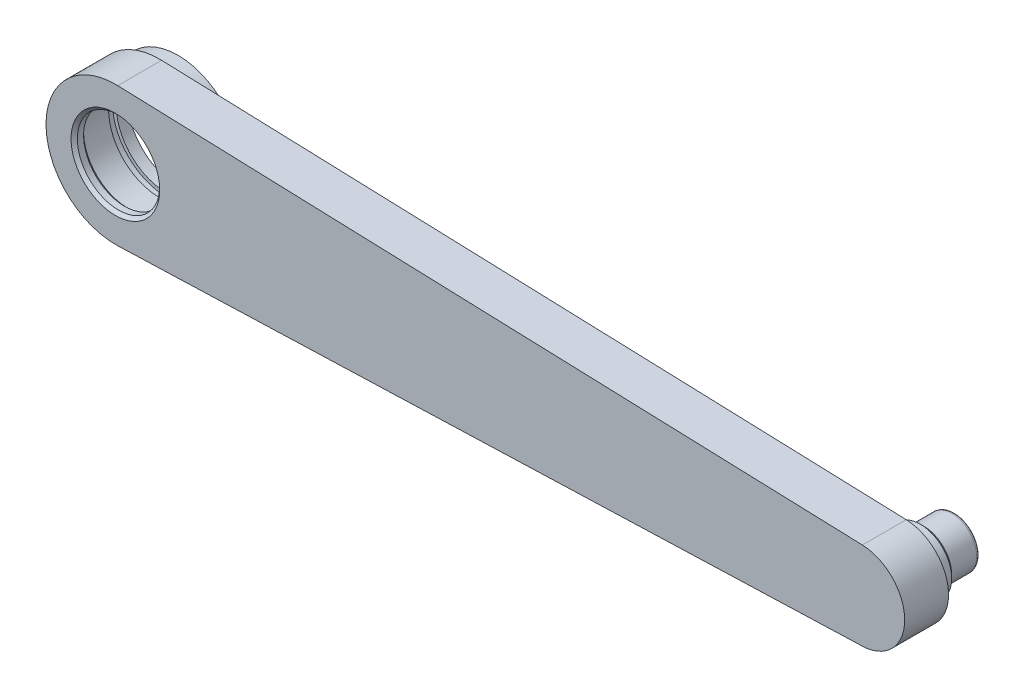
SolidWorks part; units mm, degrees
material "PEI"
ref_plane "前视基准面" through (0, 0, 0) normal (0, 0, 1) x (1, 0, 0)
ref_plane "上视基准面" through (0, 0, 0) normal (0, 1, 0) x (1, 0, 0)
ref_plane "右视基准面" through (0, 0, 0) normal (1, 0, 0) x (0, 0, -1)
other "Configuration Table"
sketch "草图1" plane through (0, 0, 0) normal (0, 0, 1) x (1, 0, 0)
  line L0 (0, 0) -> (119, 0) construction
  line L1 (0.3792, 11.0685) -> (119.2397, 6.9959)
  line L2 (0.3796, -11.0685) -> (119, -7)
  circle A0 centre (119, 0) radius 7
  circle A1 centre (0, 0) radius 8.075
  circle A2 centre (0, 0) radius 11.075
  dimension "D1" = 16.15
  dimension "D3" = 14
  dimension "D2" = 3
  dimension "D4" = 119
extrude "凸台-拉伸1" add sketch "草图1" along normal blind 7 contours A1 A2 | A2 L0 A0 L1 | L0 A2 L2 A0 | A0 region at (7.739, -7.4781, 0) region at (57.6854, 4.654, 0) region at (57.6797, -4.6531, 0) region at (114.2733, 4.8914, 0)
sketch "草图2" plane through (0, 0, 7) normal (0, 0, 1) x (1, 0, 0)
  circle A0 centre (0, 0) radius 8.075 construction
  circle A1 centre (0, 0) radius 8.075
  circle A2 centre (0, 0) radius 6.575
  dimension "D1" = 1.5
extrude "凸台-拉伸2" add sketch "草图2" against normal blind 2
sketch "草图3" plane through (0, 0, 0) normal (0, 0, -1) x (-1, 0, 0)
  arc A0 (-119.2397, 6.9959) -> (-119, -7) centre (-119, 0) ccw construction
  arc A1 (-119.2397, 6.9959) -> (-119, -7) centre (-119, 0) ccw
  circle A2 centre (-119, 0) radius 4
  dimension "D1" = 8
extrude "凸台-拉伸3" add sketch "草图3" along normal blind 10 contours A2 region at (119, 0, 0)
sketch "草图4" plane through (0, 0, 0) normal (0, 0, -1) x (-1, 0, 0)
  circle A0 centre (-119, 0) radius 4 construction
  circle A1 centre (-119, 0) radius 4
  circle A2 centre (-119, 0) radius 5
  dimension "D1" = 1
extrude "凸台-拉伸4" add sketch "草图4" along normal blind 3
chamfer "倒角1" distance 0.5 angle 45 4 edges at (6.575, 0, 7) (6.575, 0, 5) (114, 0, -3) (115, 0, -10)
chamfer "倒角2" [suppressed] distance 1 angle 45
sketch "草图5" plane through (0, 0, 0) normal (0, 0, -1) x (-1, 0, 0)
  line L0 (-0.1738, 5.072) -> (-119.0901, 0.9975)
  line L1 (-118.9996, -0.9965) -> (-0.174, -5.072)
  line L2 (-119, -7) -> (-0.3796, -11.0685)
  line L3 (-119, -7) -> (-0.3796, -11.0685)
  line L8 (-0.3792, 11.0685) -> (-119.2397, 6.9959)
  line L9 (-0.3792, 11.0685) -> (-119.2397, 6.9959)
  arc A0 (-119.0901, 0.9975) -> (-118.9996, -0.9965) centre (-119.0945, -0.0017) ccw
  arc A1 (-0.174, -5.072) -> (-0.1738, 5.072) centre (0, 0) ccw
  arc A2 (-0.3796, -11.0685) -> (-0.3792, 11.0685) centre (0, 0) ccw
  arc A3 (-0.3796, -11.0685) -> (-0.3792, 11.0685) centre (0, 0) ccw
  circle A6 centre (-119, 0) radius 5 construction
  arc A12 (-119.2397, 6.9959) -> (-119, -7) centre (-119, 0) ccw
  arc A13 (-119.2397, 6.9959) -> (-119, -7) centre (-119, 0) ccw
  circle A30 centre (0, 0) radius 8.575
  circle A31 centre (-119, 0) radius 5
  circle A32 centre (-119, 0) radius 10
  circle A33 centre (0, 0) radius 13.575
  dimension "D1" = 0
  dimension "D3" = 5
extrude "切除-拉伸1" cut sketch "草图5" against normal up to surface (7 mm away) contours A33 L0 A32 L1 region at (52.3871, 0.0009, 0) up to face at (7.075, 0, 7)
sketch "草图6" plane through (0, 0, 0) normal (0, 0, -1) x (-1, 0, 0)
  line L0 (-109.0897, -1.3364) -> (-12.7572, -4.6404) construction
  line L1 (-12.7571, 4.6409) -> (-109.0902, 1.3401) construction
  line L2 (-109.0897, -1.3364) -> (-12.7572, -4.6404)
  line L3 (-12.7571, 4.6409) -> (-109.0902, 1.3401)
  line L4 (-12.8598, 7.6391) -> (-109.1929, 4.3384)
  line L5 (-109.1925, -4.3346) -> (-12.8601, -7.6387)
  line L6 (-109.1929, 4.3384) -> (-109.0902, 1.3401)
  line L7 (-109.0897, -1.3364) -> (-109.1925, -4.3346)
  line L8 (-12.8598, 7.6391) -> (-12.7571, 4.6409)
  line L9 (-12.7572, -4.6404) -> (-12.8601, -7.6387)
  dimension "D1" = 3
extrude "切除-拉伸2" cut sketch "草图6" against normal blind 5
sketch "草图7" plane through (0, 0, 0) normal (0, 1, 0) x (1, 0, 0)
  line L0 (122.5, 10) -> (115.5, 10) construction
  line L1 (122.5, 10) -> (115.5, 10)
  line L2 (119, 10) -> (119, 0.7286) construction
  line L4 (115.3, 9) -> (115, 9)
  line L5 (115.3, 9) -> (115.3, 8)
  line L6 (115.3, 8) -> (115, 8)
  line L7 (115, 9) -> (115, 8)
  dimension "D1" = 1
  dimension "D2" = 4
  dimension "D3" = 3.7
  dimension "D4" = 2
revolve "切除-旋转1" [suppressed] cut sketch "草图7" angle 360 about L2
sketch "草图8" plane through (0, 0, -10) normal (0, 0, -1) x (-1, 0, 0)
  circle A0 centre (-119, 0) radius 4 construction
  circle A1 centre (-119, 0) radius 4
extrude "切除-拉伸3" cut sketch "草图8" against normal blind 2
fillet "圆角1" radius 0.5 1 edges at (115, 0, -8)
sketch "草图9" plane through (0, 0, -8) normal (0, 0, -1) x (-1, 0, 0)
  circle A0 centre (-119, 0) radius 2.2
  dimension "D1" = 4.4
extrude "切除-拉伸4" cut sketch "草图9" against normal blind 10
sketch "草图10" plane through (0, 0, 0) normal (0, 0, -1) x (-1, 0, 0)
  circle A0 centre (0, 0) radius 10.075
  circle A1 centre (0, 0) radius 8.075 construction
  circle A2 centre (0, 0) radius 8.075
  dimension "D1" = 2
extrude "凸台-拉伸5" add sketch "草图10" along normal blind 3
sketch "草图11" plane through (0, 0, 0) normal (0, 1, 0) x (1, 0, 0)
  line L0 (8.075, 3) -> (-8.075, 3) construction
  line L1 (5.1574, 1.2) -> (8.65, 1.2)
  line L2 (5.1574, 1.2) -> (5.1574, 0)
  line L3 (5.1574, 0) -> (8.65, 0)
  line L4 (8.65, 1.2) -> (8.65, 0)
  line L5 (0, 0) -> (0, 7.7818) construction
  dimension "D1" = 1.2
  dimension "D2" = 8.65
  dimension "D3" = 3
revolve "切除-旋转2" cut sketch "草图11" angle 360 about L5 region at (6.9037, 0, -0.6)
sketch "草图12" plane through (0, 0, 7) normal (0, 0, 1) x (1, 0, 0)
  line L0 (109.0897, -1.3364) -> (12.7572, -4.6404) construction
  line L1 (12.7571, 4.6409) -> (109.0902, 1.3401) construction
  line L2 (109.0897, -1.3364) -> (12.7572, -4.6404)
  line L3 (12.7571, 4.6409) -> (109.0902, 1.3401)
  arc A0 (109.0902, 1.3401) -> (109.0897, -1.3364) centre (119, 0) ccw construction
  arc A1 (12.7572, -4.6404) -> (12.7571, 4.6409) centre (0, 0) ccw construction
  arc A2 (109.0902, 1.3401) -> (109.0897, -1.3364) centre (119, 0) ccw
  arc A3 (12.7572, -4.6404) -> (12.7571, 4.6409) centre (0, 0) ccw
extrude "凸台-拉伸6" add sketch "草图12" against normal up to surface (2 mm away) up to face at (60.975, 4.4896, 5)
sketch "草图13" plane through (0, 0, 5) normal (0, 0, -1) x (-1, 0, 0)
  line L6 (-109.0897, -1.3364) -> (-109.1925, -4.3346)
  line L7 (-109.1925, -4.3346) -> (-12.8601, -7.6387)
  line L8 (-12.8601, -7.6387) -> (-12.7572, -4.6404)
  line L9 (-12.7571, 4.6409) -> (-12.8598, 7.6391)
  line L10 (-12.8598, 7.6391) -> (-109.1929, 4.3384)
  line L11 (-109.1929, 4.3384) -> (-109.0902, 1.3401)
  line L12 (-109.0897, -1.3364) -> (-109.1925, -4.3346)
  line L13 (-109.1925, -4.3346) -> (-12.8601, -7.6387)
  line L14 (-12.8601, -7.6387) -> (-12.7572, -4.6404)
  line L15 (-12.7571, 4.6409) -> (-12.8598, 7.6391)
  line L16 (-12.8598, 7.6391) -> (-109.1929, 4.3384)
  line L17 (-109.1929, 4.3384) -> (-109.0902, 1.3401)
  arc A2 (-12.7571, 4.6409) -> (-12.7572, -4.6404) centre (0, 0) ccw
  arc A3 (-109.0897, -1.3364) -> (-109.0902, 1.3401) centre (-119, 0) ccw
  arc A4 (-12.7571, 4.6409) -> (-12.7572, -4.6404) centre (0, 0) ccw
  arc A5 (-109.0897, -1.3364) -> (-109.0902, 1.3401) centre (-119, 0) ccw
  dimension "D1" = 0
extrude "凸台-拉伸7" add sketch "草图13" along normal up to surface (5 mm away) up to face at (61.0659, 0.0011, 0)
equation "\"D4@草图1\"= \"连接杆_后_长度\""
equation "\"连接杆_后_长度\"= 119"
